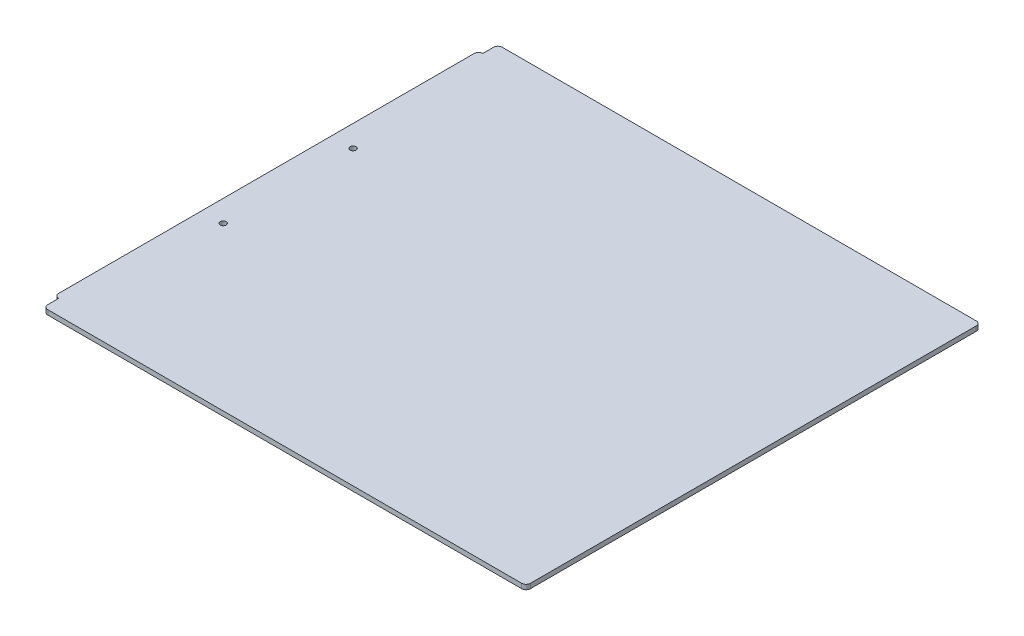
SolidWorks part; units mm, degrees
ref_plane "Front Plane" through (0, 0, 0) normal (0, 0, 1) x (1, 0, 0)
ref_plane "Top Plane" through (0, 0, 0) normal (0, 1, 0) x (1, 0, 0)
ref_plane "Right Plane" through (0, 0, 0) normal (1, 0, 0) x (0, 0, -1)
sketch "Sketch1" plane through (0, 0, 0) normal (0, 1, 0) x (1, 0, 0)
  line L1 (0, 0) -> (304.8, 0)
  line L2 (0, 0) -> (0, 304.8)
  line L3 (0, 304.8) -> (304.8, 304.8)
  line L4 (304.8, 0) -> (304.8, 304.8)
  dimension "D1" = 304.8
  dimension "D2" = 304.8
extrude "Boss-Extrude1" add sketch "Sketch1" along normal blind 2.7781
sketch "Sketch2" plane through (0, 2.7781, 0) normal (0, 1, 0) x (1, 0, 0)
  line L0 (304.8, 0) -> (304.8, 304.8) construction
  line L1 (0, 0) -> (304.8, 0)
  line L2 (0, 0) -> (0, 19.05)
  line L3 (0, 19.05) -> (304.8, 19.05)
  line L4 (304.8, 0) -> (304.8, 19.05)
  line L6 (0, 304.8) -> (304.8, 304.8)
  line L7 (0, 304.8) -> (0, 285.75)
  line L8 (0, 285.75) -> (304.8, 285.75)
  line L9 (304.8, 304.8) -> (304.8, 285.75)
  dimension "D1" = 19.05
  dimension "D2" = 19.05
extrude "Cut-Extrude1" cut sketch "Sketch2" against normal through all
sketch "Sketch4" plane through (0, 2.7781, 0) normal (0, 1, 0) x (1, 0, 0)
  line L0 (304.8, 19.05) -> (0, 19.05) construction
  line L1 (0, 285.75) -> (0, 19.05) construction
  circle A0 centre (12.7, 190.5762) radius 1.7526
  circle A1 centre (12.7, 114.3762) radius 1.7526
  dimension "D1" = 3.5052
  dimension "D4" = 12.7
  dimension "D2" = 76.2
  dimension "D3" = 95.3262
extrude "Cut-Extrude3" cut sketch "Sketch4" against normal through all
sketch "Sketch5" plane through (0, 2.7781, 0) normal (0, 1, 0) x (1, 0, 0)
  line L0 (304.8, 19.05) -> (0, 19.05) construction
  line L1 (304.8, 285.75) -> (285.75, 285.75)
  line L2 (304.8, 285.75) -> (304.8, 19.05)
  line L3 (304.8, 19.05) -> (285.75, 19.05)
  line L4 (285.75, 285.75) -> (285.75, 19.05)
  dimension "D1" = 19.05
extrude "Cut-Extrude4" cut sketch "Sketch5" against normal through all
sketch "Sketch6" plane through (0, 2.7781, 0) normal (0, 1, 0) x (1, 0, 0)
  line L0 (0, 285.75) -> (285.75, 285.75) construction
  line L1 (0, 285.75) -> (2.54, 285.75)
  line L2 (0, 285.75) -> (0, 276.86)
  line L3 (0, 276.86) -> (2.54, 276.86)
  line L4 (2.54, 285.75) -> (2.54, 276.86)
  line L5 (0, 285.75) -> (0, 19.05) construction
  line L7 (0, 19.05) -> (2.54, 19.05)
  line L8 (0, 19.05) -> (0, 27.94)
  line L9 (0, 27.94) -> (2.54, 27.94)
  line L10 (2.54, 19.05) -> (2.54, 27.94)
  dimension "D1" = 8.89
  dimension "D2" = 2.54
extrude "Cut-Extrude5" cut sketch "Sketch6" against normal through all
fillet "Fillet1" radius 2.54 6 edges at (285.75, 1.3891, -19.05) (285.75, 1.3891, -285.75) (0, 1.3891, -276.86) (2.54, 1.3891, -285.75) (2.54, 1.3891, -19.05) (0, 1.3891, -27.94)
